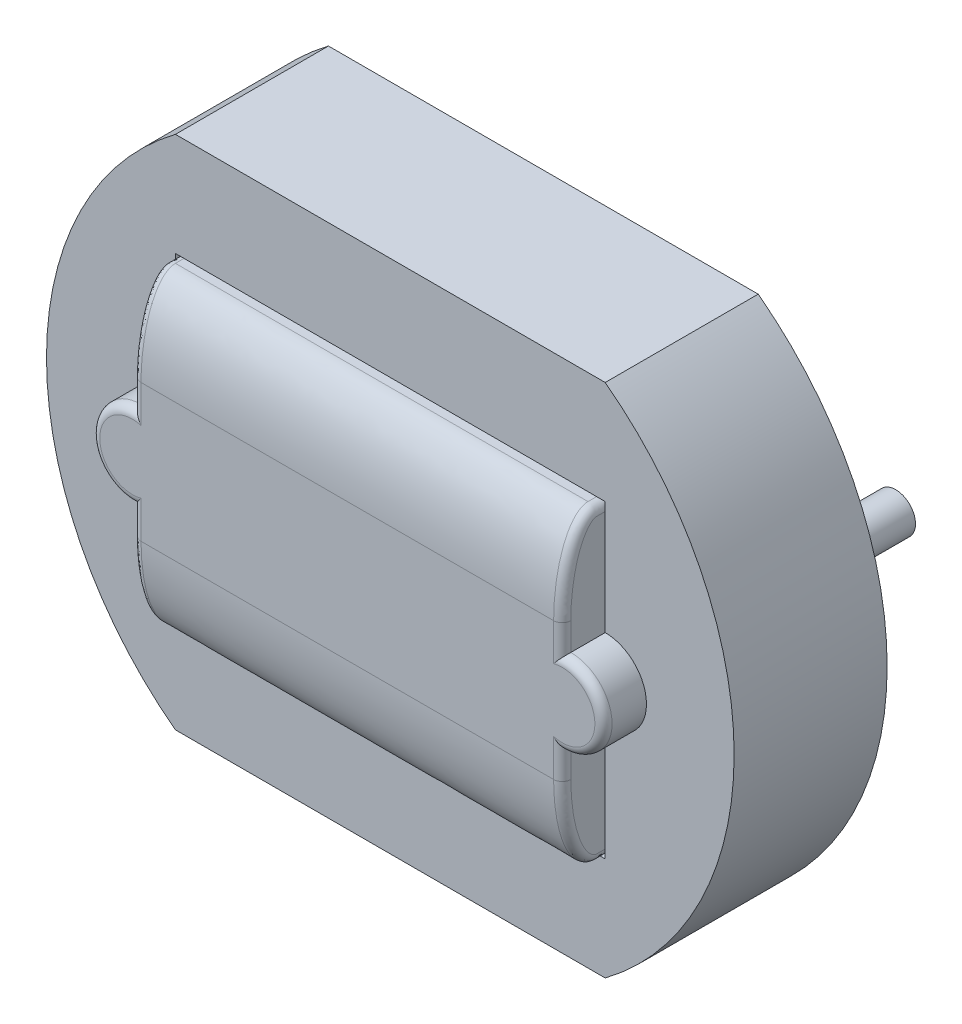
SolidWorks part; units mm, degrees
ref_plane "Front Plane" through (0, 0, 0) normal (0, 0, 1) x (1, 0, 0)
ref_plane "Top Plane" through (0, 0, 0) normal (0, 1, 0) x (1, 0, 0)
ref_plane "Right Plane" through (0, 0, 0) normal (1, 0, 0) x (0, 0, -1)
sketch "Sketch1" plane through (0, 0, 0) normal (0, 0, 1) x (1, 0, 0)
  line L0 (0, 3) -> (0, -3) construction
  line L1 (-2.5, -3) -> (2.5, -3)
  line L2 (-2.5, -3) -> (-2.5, 3) construction
  line L3 (-2.5, 3) -> (2.5, 3)
  line L4 (2.5, -3) -> (2.5, 3) construction
  line L5 (-2.5, -3) -> (2.5, 3) construction
  line L6 (-2.5, 3) -> (2.5, -3) construction
  line L7 (-4, 0) -> (4, 0) construction
  arc A0 (-2.5, 3) -> (-2.5, -3) centre (-0.25, 0) ccw
  arc A1 (2.5, 3) -> (2.5, -3) centre (0.25, 0) cw
  point P0 (0, 0)
  point P12 (0, 0)
  dimension "D1" = 5
  dimension "D2" = 6
  dimension "D3" = 8
extrude "Boss-Extrude1" add sketch "Sketch1" along normal blind 1.78
sketch "Sketch2" plane through (0, 0, 0) normal (0, 0, -1) x (-1, 0, 0)
  line L0 (0, 0) -> (2.5, 0) construction
  line L1 (0, 0) -> (-2.5, 0) construction
  circle A0 centre (-2.5, 0) radius 0.23
  circle A1 centre (2.5, 0) radius 0.23
  dimension "D1" = 0.46
  dimension "D2" = 5
extrude "Boss-Extrude2" add sketch "Sketch2" along normal blind 1.6 separate body
sketch "Sketch3" plane through (0, 0, 1.78) normal (0, 0, 1) x (1, 0, 0)
  line L0 (-2.5, 1.8) -> (-2.5, 0.48)
  line L1 (-2.5, -1.8) -> (2.5, -1.8)
  line L2 (-2.5, -1.8) -> (-2.5, 1.8) construction
  line L3 (-2.5, 1.8) -> (2.5, 1.8)
  line L4 (2.5, -1.8) -> (2.5, 1.8) construction
  line L5 (-2.5, -1.8) -> (2.5, 1.8) construction
  line L6 (-2.5, 1.8) -> (2.5, -1.8) construction
  line L7 (-2.5, -1.8) -> (-2.5, -0.48)
  line L8 (2.5, -1.8) -> (2.5, -0.48)
  line L9 (2.5, 1.8) -> (2.5, 0.48)
  arc A0 (2.5, -0.48) -> (2.5, 0.48) centre (2.5, 0) ccw
  arc A1 (-2.5, 0.48) -> (-2.5, -0.48) centre (-2.5, 0) ccw
  circle A3 centre (2.5, 0) radius 0.23
  circle A4 centre (2.5, 0) radius 0.23 construction
  point P0 (0, 0)
  dimension "D4" = 0.25
  dimension "D1" = 5
  dimension "D2" = 3.6
  dimension "D3" = 0
extrude "Cut-Extrude1" cut sketch "Sketch3" against normal blind 0.75
sketch "Sketch4" plane through (0, 0, 1.03) normal (0, 0, 1) x (1, 0, 0)
  circle A0 centre (-2.5, 0) radius 0.23 construction
  circle A1 centre (2.5, 0) radius 0.23 construction
  circle A6 centre (-2.5, 0) radius 0.23
  circle A7 centre (2.5, 0) radius 0.23
extrude "Cut-Extrude2" cut sketch "Sketch4" against normal up to next (1.03 mm away)
sketch "Sketch5" plane through (0, 0, 0) normal (0, 0, 1) x (1, 0, 0)
  circle A0 centre (2.5, 0) radius 0.23 construction
  circle A1 centre (-2.5, 0) radius 0.23 construction
  circle A2 centre (2.5, 0) radius 0.23
  circle A3 centre (-2.5, 0) radius 0.23
extrude "Boss-Extrude3" add sketch "Sketch5" along normal blind 0.25 and the other way up to surface from surface separate body other way up to face at (-2.73, 0, 0) starting at face at (-2.27, 0, 1.03)
sketch "Sketch6" plane through (0, 0, 1.03) normal (0, 0, 1) x (1, 0, 0)
  line L1 (-1.135, -1.135) -> (1.135, -1.135)
  line L2 (-1.135, -1.135) -> (-1.135, 1.135)
  line L3 (-1.135, 1.135) -> (1.135, 1.135)
  line L4 (1.135, -1.135) -> (1.135, 1.135)
  line L5 (-1.135, -1.135) -> (1.135, 1.135) construction
  line L6 (-1.135, 1.135) -> (1.135, -1.135) construction
  point P0 (0, 0)
  dimension "D1" = 2.27
extrude "Boss-Extrude4" add sketch "Sketch6" along normal blind 0.25 separate body
combine bodies "Combine1" operation type add bodies to combine 106 102
combine bodies "Combine2" operation type add bodies to combine 103 107
sketch "Sketch7" plane through (0, 0, 1.78) normal (0, 0, 1) x (1, 0, 0)
  line L6 (2.5, 0.48) -> (2.5, 1.8)
  line L7 (2.5, 1.8) -> (-2.5, 1.8)
  line L8 (-2.5, 1.8) -> (-2.5, 0.48)
  line L9 (-2.5, -0.48) -> (-2.5, -1.8)
  line L10 (-2.5, -1.8) -> (2.5, -1.8)
  line L11 (2.5, -1.8) -> (2.5, -0.48)
  line L12 (2.5, 0.48) -> (2.5, 1.8)
  line L13 (2.5, 1.8) -> (-2.5, 1.8)
  line L14 (-2.5, 1.8) -> (-2.5, 0.48)
  line L15 (-2.5, -0.48) -> (-2.5, -1.8)
  line L16 (-2.5, -1.8) -> (2.5, -1.8)
  line L17 (2.5, -1.8) -> (2.5, -0.48)
  arc A2 (-2.5, 0.48) -> (-2.5, -0.48) centre (-2.5, 0) ccw
  arc A3 (2.5, -0.48) -> (2.5, 0.48) centre (2.5, 0) ccw
  arc A4 (-2.5, 0.48) -> (-2.5, -0.48) centre (-2.5, 0) ccw
  arc A5 (2.5, -0.48) -> (2.5, 0.48) centre (2.5, 0) ccw
  dimension "D1" = 0
extrude "Boss-Extrude6" add sketch "Sketch7" along normal blind 0.5 and the other way up to vertex (0.75 mm away) separate body other way up to point (-2.5, -1.8, 1.03)
fillet "Fillet1" radius 0.4 2 edges at (0, 1.8, 2.28) (0, -1.8, 2.28) second distance 1 first distance on face at (0, 1.8, 1.655) first distance on face at (0, -1.8, 1.655)
fillet "Fillet2" radius 0.1 10 edges at (-2.98, 0, 2.28) (2.98, 0, 2.28) tangent propagation no
